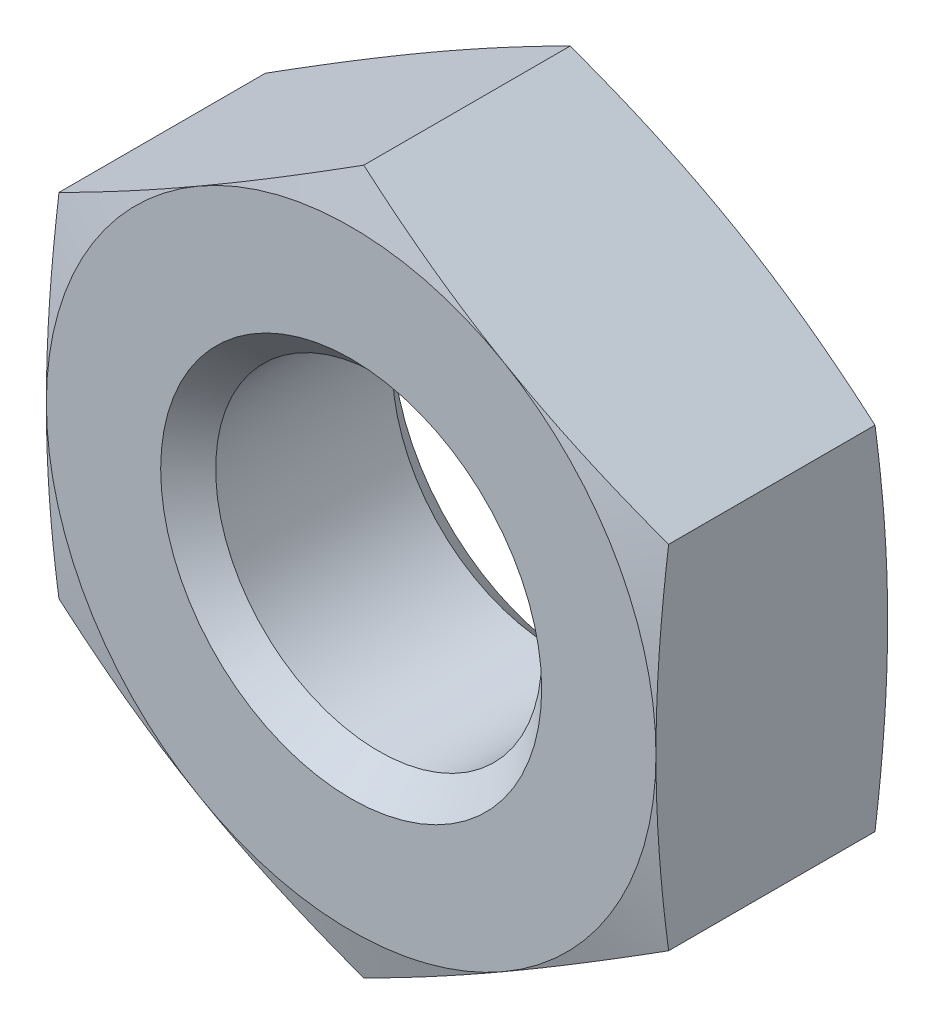
SolidWorks part; units mm, degrees
material "AISI 1045 Steel, cold drawn"
ref_plane "Front Plane" through (0, 0, 0) normal (0, 0, 1) x (1, 0, 0)
ref_plane "Top Plane" through (0, 0, 0) normal (0, 1, 0) x (1, 0, 0)
ref_plane "Right Plane" through (0, 0, 0) normal (1, 0, 0) x (0, 0, -1)
sketch "Sketch1" plane through (0, 0, 0) normal (1, 0, 0) x (0, 0, -1)
  line L0 (0, 0) -> (0, 6.35)
  line L1 (0, 6.35) -> (0.3403, 7.62)
  line L2 (0.3403, 7.62) -> (4.4857, 7.62)
  line L3 (4.4857, 7.62) -> (4.826, 6.35)
  line L4 (4.826, 6.35) -> (4.826, 0)
  line L5 (4.826, 0) -> (0, 0)
  line L6 (4.826, 0) -> (0, 0) construction
sketch "Sketch2" plane through (0, 0, 0) normal (0, 0, 1) x (1, 0, 0)
  line L0 (-12.7, 12.7) -> (-12.7, -12.7)
  line L1 (-12.7, -12.7) -> (12.7, -12.7)
  line L2 (12.7, -12.7) -> (12.7, 12.7)
  line L3 (12.7, 12.7) -> (-12.7, 12.7)
  line L4 (-6.35, 3.6662) -> (-6.35, -3.6662)
  line L5 (-6.35, -3.6662) -> (0, -7.3323)
  line L6 (0, -7.3323) -> (6.35, -3.6662)
  line L7 (6.35, -3.6662) -> (6.35, 3.6662)
  line L8 (6.35, 3.6662) -> (0, 7.3323)
  line L9 (0, 7.3323) -> (-6.35, 3.6662)
revolve "Revolve1" add sketch "Sketch1" angle 360 about L6 reverse direction yes
extrude "Cut-Extrude1" cut sketch "Sketch2" against normal blind 4.826
sketch "Sketch3" plane through (0, 0, 0) normal (1, 0, 0) x (0, 0, -1)
  line L0 (0, 0) -> (0, 3.9688)
  line L1 (0, 3.9688) -> (0.5728, 3.396)
  line L2 (0.5728, 3.396) -> (4.2532, 3.396)
  line L3 (4.2532, 3.396) -> (4.826, 3.9688)
  line L4 (4.826, 3.9688) -> (4.826, 0)
  line L5 (4.826, 0) -> (0, 0)
  line L6 (4.826, 0) -> (0, 0) construction
revolve "Cut-Revolve1" cut sketch "Sketch3" angle 360 about L6 reverse direction yes
cosmetic thread "Cosmetic Thread1" parameters "D1"=4.826, "D2"=7.9375
ref_plane "NUT XY" through (0, 0, 0) normal (0, 0, 1) x (1, 0, 0)
ref_plane "NUT XZ" through (0, 0, 0) normal (0, -1, 0) x (-1, 0, 0)
ref_plane "NUT YZ" through (0, 0, 0) normal (1, 0, 0) x (0, 0, -1)
ref_axis "NUT X" through (-80.9, 0, 0) along (1, 0, 0)
ref_axis "NUT Y" through (0, -50, 0) along (0, 1, 0)
ref_axis "NUT Z" through (0, 0, 80.9) along (0, 0, -1)
sketch3d "NUT"
  point P0 (0, 0, 0)
ref_plane "a1 XY" through (0, 0, 0) normal (0, 0, 1) x (1, 0, 0)
ref_plane "a1 XZ" through (0, 6.35, 0) normal (0, -1, 0) x (-1, 0, 0)
ref_plane "a1 YZ" through (-6.35, 0, 0) normal (1, 0, 0) x (0, 0, -1)
ref_axis "a1 X" through (-80.9, 6.35, 0) along (1, 0, 0)
ref_axis "a1 Y" through (-6.35, -50, 0) along (0, 1, 0)
ref_axis "a1 Z" through (-6.35, 6.35, 80.9) along (0, 0, -1)
sketch3d "a1"
  point P0 (-6.35, 6.35, 0)
ref_plane "a2 XY" through (0, 0, 0) normal (0, 0, 1) x (1, 0, 0)
ref_plane "a2 XZ" through (0, 6.35, 0) normal (0, -1, 0) x (-1, 0, 0)
ref_plane "a2 YZ" through (6.35, 0, 0) normal (1, 0, 0) x (0, 0, -1)
ref_axis "a2 X" through (-80.9, 6.35, 0) along (1, 0, 0)
ref_axis "a2 Y" through (6.35, -50, 0) along (0, 1, 0)
ref_axis "a2 Z" through (6.35, 6.35, 80.9) along (0, 0, -1)
sketch3d "a2"
  point P0 (6.35, 6.35, 0)
ref_plane "b1 XY" through (0, 0, 0) normal (1, 0, 0) x (0, 0, -1)
ref_plane "b1 XZ" through (0, 6.35, 0) normal (0, -1, 0) x (-1, 0, 0)
ref_plane "b1 YZ" through (0, 0, 0) normal (0, 0, -1) x (-1, 0, 0)
ref_axis "b1 X" through (0, 6.35, 80.9) along (0, 0, -1)
ref_axis "b1 Y" through (0, -50, 0) along (0, 1, 0)
ref_axis "b1 Z" through (80.9, 6.35, 0) along (-1, 0, 0)
sketch3d "b1"
  point P0 (0, 6.35, 0)
ref_plane "b2 XY" through (0, 0, 0) normal (1, 0, 0) x (0, 0, -1)
ref_plane "b2 XZ" through (0, 6.35, 0) normal (0, -1, 0) x (-1, 0, 0)
ref_plane "b2 YZ" through (0, 0, -4.826) normal (0, 0, -1) x (-1, 0, 0)
ref_axis "b2 X" through (0, 6.35, 80.9) along (0, 0, -1)
ref_axis "b2 Y" through (0, -50, -4.826) along (0, 1, 0)
ref_axis "b2 Z" through (80.9, 6.35, -4.826) along (-1, 0, 0)
sketch3d "b2"
  point P0 (0, 6.35, -4.826)
ref_plane "e XY" through (0, 0, 0) normal (1, 0, 0) x (0, 0, -1)
ref_plane "e XZ" through (0, 0, 0) normal (0, -1, 0) x (-1, 0, 0)
ref_plane "e YZ" through (0, 0, -4.826) normal (0, 0, -1) x (-1, 0, 0)
ref_axis "e X" through (0, 0, 80.9) along (0, 0, -1)
ref_axis "e Y" through (0, -50, -4.826) along (0, 1, 0)
ref_axis "e Z" through (80.9, 0, -4.826) along (-1, 0, 0)
sketch3d "e"
  point P0 (0, 0, -4.826)
ref_plane "ol1 XY" through (0, 0, 0) normal (0, 1, 0) x (1, 0, 0)
ref_plane "ol1 XZ" through (0, 0, -6.35) normal (0, 0, 1) x (1, 0, 0)
ref_plane "ol1 YZ" through (0, 0, 0) normal (1, 0, 0) x (0, 0, -1)
ref_axis "ol1 X" through (-80.9, 0, -6.35) along (1, 0, 0)
ref_axis "ol1 Y" through (0, 0, 50) along (0, 0, -1)
ref_axis "ol1 Z" through (0, 50, -6.35) along (0, -1, 0)
sketch3d "ol1"
  point P0 (0, 0, -6.35)
ref_plane "ol2 XY" through (0, 0, 0) normal (0, 1, 0) x (1, 0, 0)
ref_plane "ol2 XZ" through (0, 0, -6.35) normal (0, 0, 1) x (1, 0, 0)
ref_plane "ol2 YZ" through (4.826, 0, 0) normal (1, 0, 0) x (0, 0, -1)
ref_axis "ol2 X" through (-80.9, 0, -6.35) along (1, 0, 0)
ref_axis "ol2 Y" through (4.826, 0, 50) along (0, 0, -1)
ref_axis "ol2 Z" through (4.826, 50, -6.35) along (0, -1, 0)
sketch3d "ol2"
  point P0 (4.826, 0, -6.35)
ref_plane "th1 XY" through (0, 0, 0) normal (1, 0, 0) x (0, 0, -1)
ref_plane "th1 XZ" through (0, 3.9688, 0) normal (0, -1, 0) x (-1, 0, 0)
ref_plane "th1 YZ" through (0, 0, -4.826) normal (0, 0, -1) x (-1, 0, 0)
ref_axis "th1 X" through (0, 3.9688, 80.9) along (0, 0, -1)
ref_axis "th1 Y" through (0, -50, -4.826) along (0, 1, 0)
ref_axis "th1 Z" through (80.9, 3.9688, -4.826) along (-1, 0, 0)
sketch3d "th1"
  point P0 (0, 3.9688, -4.826)
ref_plane "th2 XY" through (0, 0, 0) normal (1, 0, 0) x (0, 0, -1)
ref_plane "th2 XZ" through (0, -3.9688, 0) normal (0, -1, 0) x (-1, 0, 0)
ref_plane "th2 YZ" through (0, 0, -4.826) normal (0, 0, -1) x (-1, 0, 0)
ref_axis "th2 X" through (0, -3.9688, 80.9) along (0, 0, -1)
ref_axis "th2 Y" through (0, -50, -4.826) along (0, 1, 0)
ref_axis "th2 Z" through (80.9, -3.9688, -4.826) along (-1, 0, 0)
sketch3d "th2"
  point P0 (0, -3.9688, -4.826)
